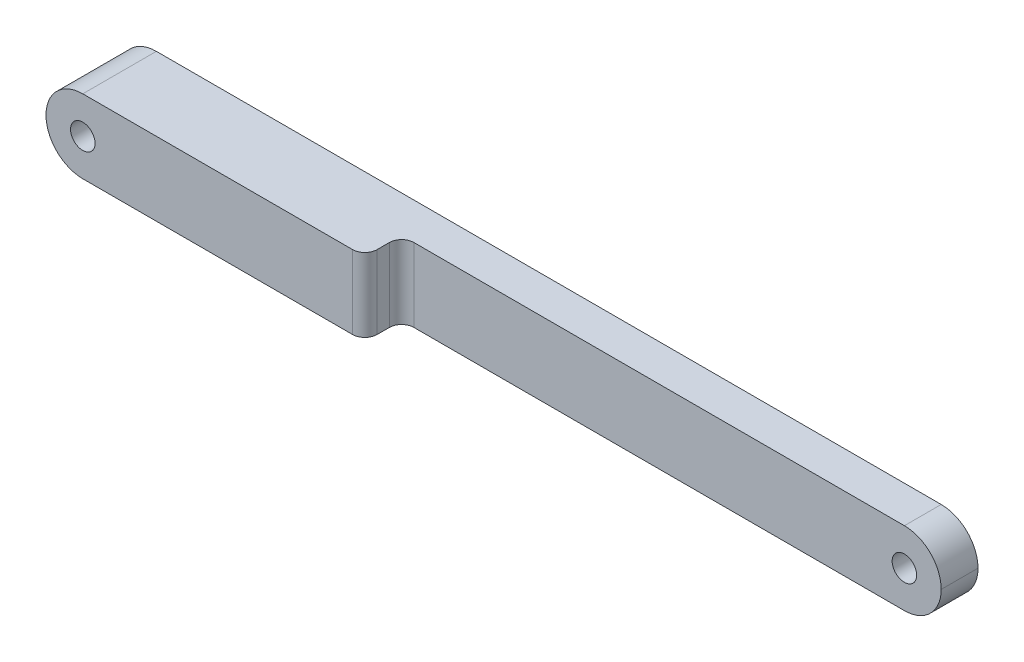
SolidWorks part; units mm, degrees
material "6061 Alloy"
ref_plane "Front Plane" through (0, 0, 0) normal (0, 0, 1) x (1, 0, 0)
ref_plane "Top Plane" through (0, 0, 0) normal (0, 1, 0) x (1, 0, 0)
ref_plane "Right Plane" through (0, 0, 0) normal (1, 0, 0) x (0, 0, -1)
sketch "Sketch1" plane through (0, 0, 0) normal (0, 0, 1) x (1, 0, 0)
  line L0 (0, 0) -> (0, 30)
  line L1 (0, 30) -> (350, 30)
  line L2 (350, 30) -> (350, 0)
  line L3 (350, 0) -> (0, 0)
  dimension "D1" = 30
  dimension "D2" = 350
extrude "Boss-Extrude1" add sketch "Sketch1" along normal mid plane 30
sketch "Sketch3" plane through (0, 0, 15) normal (0, 0, 1) x (1, 0, 0)
  line L0 (0, 15) -> (15, 15) construction
  line L1 (0, 30) -> (0, 0) construction
  line L2 (335, 15) -> (350, 15) construction
  line L3 (350, 0) -> (350, 30) construction
  circle A0 centre (15, 15) radius 5
  circle A1 centre (335, 15) radius 5
  dimension "D1" = 10
  dimension "D2" = 10
  dimension "D3" = 15
  dimension "D4" = 15
extrude "Cut-Extrude2" cut sketch "Sketch3" against normal through all both and the other way through all
fillet "Fillet3" radius 15 4 edges at (350, 0, 0) (350, 30, 0) (0, 0, 0) (0, 30, 0)
sketch "Sketch4" plane through (0, 0, 15) normal (0, 0, 1) x (1, 0, 0)
  line L0 (130, 0) -> (130, 30)
  line L1 (15, 0) -> (335, 0) construction
  line L2 (335, 30) -> (15, 30) construction
  circle M3 centre (335, 15) radius 5
  line M6 (15, 0) -> (335, 0)
  arc M7 (335, 0) -> (350, 15) centre (335, 15) ccw
  arc M8 (350, 15) -> (335, 30) centre (335, 15) ccw
  line M9 (335, 30) -> (15, 30)
  dimension "D1" = 220
extrude "Cut-Extrude3" cut sketch "Sketch4" against normal blind 10 and the other way through all contours L0 M6 M7 M8 M9 M3
fillet "Fillet4" radius 5 1 edges at (130, 15, 15)
sketch "Sketch6" plane through (0, 0, 0) normal (0, -1, 0) x (1, 0, 0)
  line L0 (375, 5) -> (375, 0)
  line L1 (130, 5) -> (335, 5) construction
  line L2 (375, 0) -> (130, 0)
  line L3 (130, 0) -> (130, 5)
  line L4 (130, 5) -> (375, 5)
  line L5 (335, -15) -> (335, 5) construction
  dimension "D1" = 40
  dimension "D2" = 245
  dimension "D3" = 5
extrude "Cut-Extrude4" cut sketch "Sketch6" against normal up to next
fillet "Fillet6" radius 5 1 edges at (130, 15, 0)
